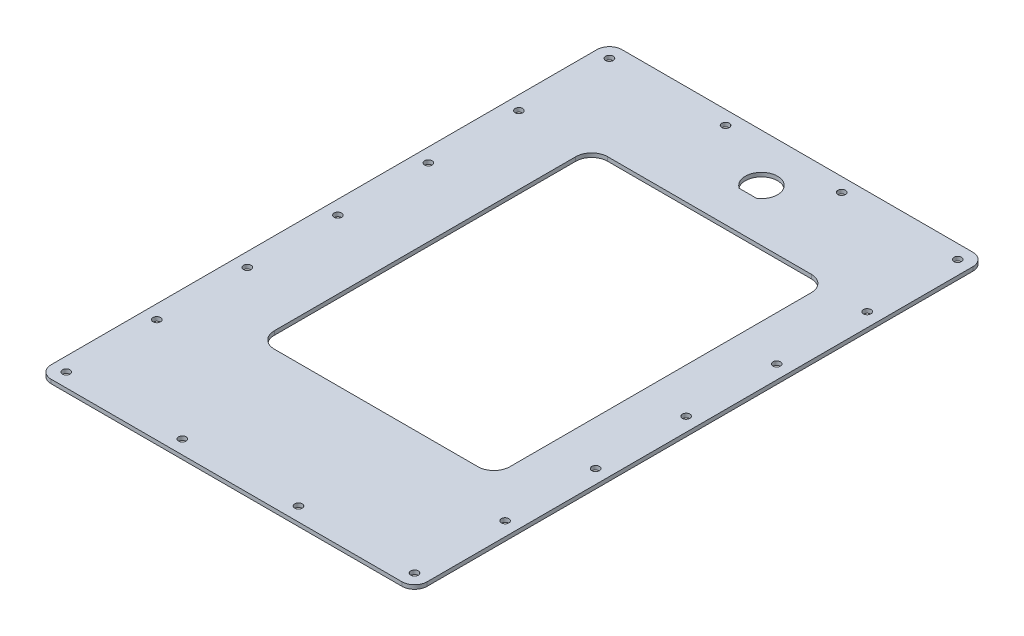
SolidWorks part; units mm, degrees
material "5052-H32"
ref_plane "Front Plane" through (0, 0, 0) normal (0, 0, 1) x (1, 0, 0)
ref_plane "Top Plane" through (0, 0, 0) normal (0, 1, 0) x (1, 0, 0)
ref_plane "Right Plane" through (0, 0, 0) normal (1, 0, 0) x (0, 0, -1)
sketch "Sketch9" plane through (0, 0, 0) normal (0, 1, 0) x (1, 0, 0)
  line L0 (-149.5, 0) -> (-149.5, 454)
  line L13 (-149.5, 454) -> (149.5, 454)
  line L14 (103.1625, 109.4438) -> (-84.1625, 109.4438)
  line L19 (149.5, 454) -> (149.5, 0)
  line L20 (103.1625, 109.4438) -> (103.1625, 374.5563)
  line L21 (103.1625, 374.5563) -> (-84.1625, 374.5563)
  line L22 (-84.1625, 109.4438) -> (-84.1625, 374.5563)
  line L23 (103.1625, 242) -> (-84.1625, 242) construction
  line L24 (9.5, 374.5562) -> (9.5, 109.4438) construction
  line L25 (-149.5, 0) -> (149.5, 0)
  line L26 (9.5, 454) -> (9.5, 415.9) construction
  line L27 (16.3702, 405.1) -> (2.6298, 405.1)
  arc A0 (16.3702, 405.1) -> (2.6298, 405.1) centre (9.5, 415.9) ccw
  point P8 (0, 0)
  point P17 (9.5, 428.7)
  point P19 (0, 0)
  dimension "D8" = 25.6
  dimension "D3" = 265.1125
  dimension "D4" = 187.325
  dimension "D1" = 299
  dimension "D2" = 454
  dimension "D6" = 140
  dimension "D5" = 212
  dimension "D7" = 23.6
  dimension "D9" = 38.1
extrude "Boss-Extrude7" add sketch "Sketch9" along normal blind 3.175 separate body contours L0 L25 L19 L13 L14 L22 L21 L20 region at (-144.0639, 0, -227)
fillet "Fillet4" radius 10 4 edges at (-149.5, 1.5875, -454) (149.5, 1.5875, -454) (-149.5, 1.5875, 0) (149.5, 1.5875, 0)
fillet "Fillet5" radius 12.7 4 edges at (-84.1625, 1.5875, -109.4438) (103.1625, 1.5875, -109.4438) (103.1625, 1.5875, -374.5563) (-84.1625, 1.5875, -374.5563)
sketch "Sketch10" plane through (0, 3.175, 0) normal (0, 1, 0) x (1, 0, 0)
  line L0 (-149.5, 10) -> (-149.5, 444) construction
  line L1 (-139.5, 0) -> (139.5, 0) construction
  circle A0 centre (-138.5, 11) radius 3
  circle A1 centre (-46.1667, 11) radius 3
  circle A2 centre (46.1667, 11) radius 3
  circle A3 centre (138.5, 11) radius 3
  circle A56 centre (-138.5, 83) radius 3
  circle A57 centre (-138.5, 155) radius 3
  circle A58 centre (-138.5, 227) radius 3
  circle A59 centre (-138.5, 299) radius 3
  circle A60 centre (-138.5, 371) radius 3
  circle A61 centre (-138.5, 443) radius 3
  circle A68 centre (138.5, 83) radius 3
  circle A72 centre (138.5, 155) radius 3
  circle A76 centre (138.5, 227) radius 3
  circle A80 centre (138.5, 299) radius 3
  circle A84 centre (138.5, 371) radius 3
  circle A86 centre (-46.1667, 443) radius 3
  circle A87 centre (46.1667, 443) radius 3
  circle A88 centre (138.5, 443) radius 3
  circle A102 centre (-46.1667, 83) radius 3 [skipped]
  circle A103 centre (46.1667, 83) radius 3 [skipped]
  circle A104 centre (-46.1667, 155) radius 3 [skipped]
  circle A105 centre (46.1667, 155) radius 3 [skipped]
  circle A106 centre (-46.1667, 227) radius 3 [skipped]
  circle A107 centre (46.1667, 227) radius 3 [skipped]
  circle A108 centre (-46.1667, 299) radius 3 [skipped]
  circle A109 centre (46.1667, 299) radius 3 [skipped]
  circle A110 centre (-46.1667, 371) radius 3 [skipped]
  circle A111 centre (46.1667, 371) radius 3 [skipped]
  dimension "D1" = 6
  dimension "D2" = 11
  dimension "D3" = 11
  dimension "D6" = 72
  dimension "D7" = 92.3333
  dimension "D4" = 4
  dimension "D5" = 7
extrude "Cut-Extrude1" cut sketch "Sketch10" against normal up to surface (3.175 mm away) up to face at (9.5, 0, -416.9)
equation "\"W\"= 255mm"
equation "\"L\"= 410mm"
equation "\"Offset\"= 13mm"
equation "\"H\"= 110mm"
equation "\"Compartment Width\"= 80"
equation "\"T\"= 4.7625 * 2 / 3mm"
equation "\"Inside Fillet Radius\"= 5.55625mm"
equation "\"Hole\"=15mm"
equation "\"Wheel to Wall\"= 43"
equation "\"D1@Sketch9\"=\"W\"+44"
equation "\"D2@Sketch9\"=\"L\"+44"
equation "\"D6@Sketch10\"=(\"L\"+22)/6"
equation "\"D7@Sketch10\"=(\"W\"+22)/3"
equation "\"D5@Sketch9\"=(\"L\"/2+20)-\"Offset\""
